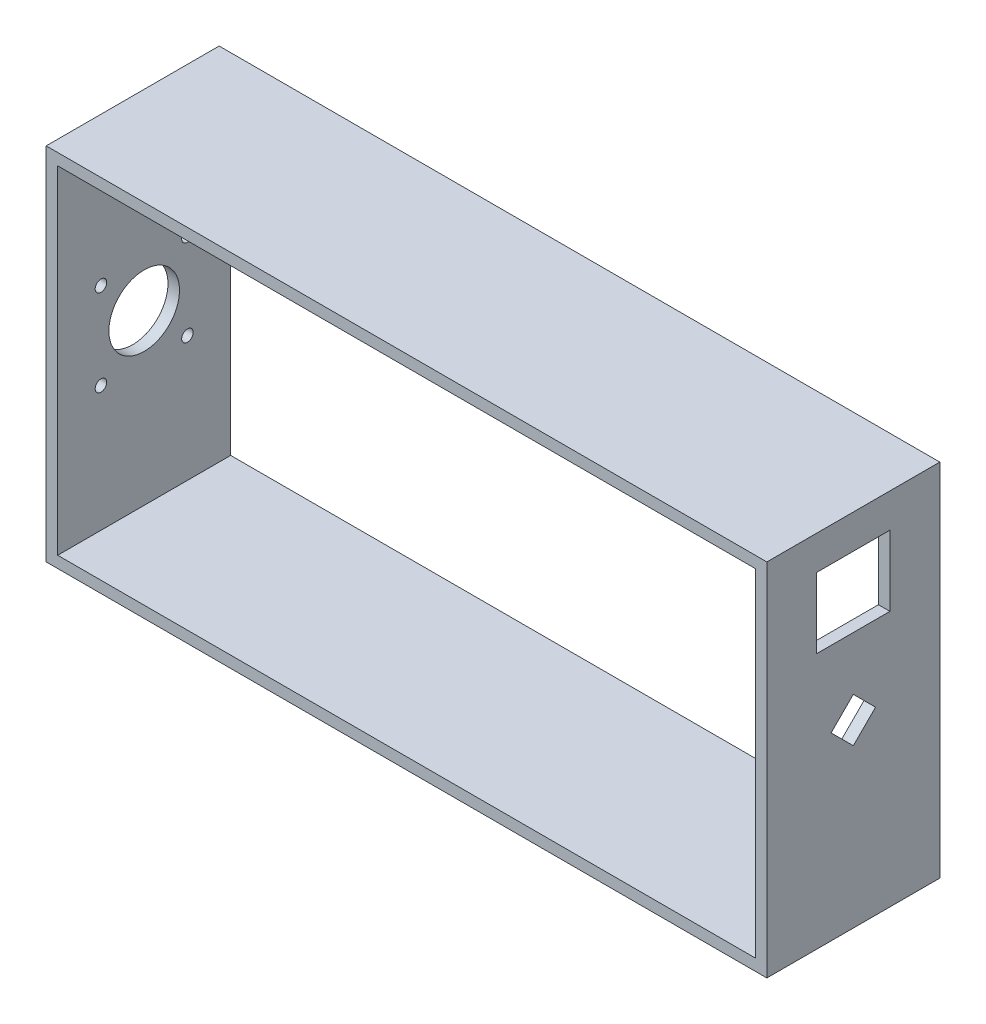
SolidWorks part; units mm, degrees
ref_plane "Ebene vorne" through (0, 0, 0) normal (0, 0, 1) x (1, 0, 0)
ref_plane "Ebene oben" through (0, 0, 0) normal (0, 1, 0) x (1, 0, 0)
ref_plane "Ebene rechts" through (0, 0, 0) normal (1, 0, 0) x (0, 0, -1)
sketch "Skizze1" plane through (0, 0, 0) normal (0, 0, 1) x (1, 0, 0)
  line L1 (0, 125) -> (250, 125)
  line L2 (0, 125) -> (0, 0)
  line L3 (0, 0) -> (250, 0)
  line L4 (250, 125) -> (250, 0)
  line L5 (246, 121) -> (4, 121)
  line L6 (246, 121) -> (246, 4)
  line L7 (246, 4) -> (4, 4)
  line L8 (4, 121) -> (4, 4)
  dimension "D1" = 250
  dimension "D2" = 125
  dimension "D3" = 4
  dimension "D4" = 4
  dimension "D5" = 4
  dimension "D6" = 4
extrude "Aufsatz-Linear austragen1" add sketch "Skizze1" along normal blind 60
sketch "Skizze2" plane through (0, 0, 0) normal (-1, 0, 0) x (0, 0, 1)
  line L0 (0, 62.5) -> (60, 62.5) construction
  line L1 (30, 125) -> (30, 0) construction
  line L2 (60, 125) -> (0, 125) construction
  line L3 (60, 0) -> (0, 0) construction
  line L4 (0, 125) -> (0, 0) construction
  line L5 (60, 125) -> (60, 0) construction
  line L6 (15, 77.5) -> (45, 77.5) construction
  line L7 (45, 77.5) -> (45, 47.5) construction
  line L8 (45, 47.5) -> (15, 47.5) construction
  line L9 (15, 47.5) -> (15, 77.5) construction
  circle A0 centre (30, 62.5) radius 12.25
  circle A1 centre (15, 77.5) radius 2
  circle A2 centre (45, 77.5) radius 2
  circle A3 centre (45, 47.5) radius 2
  circle A4 centre (15, 47.5) radius 2
  point P17 (30, 62.5)
  point P21 (30, 77.5)
  point P22 (53.5816, 62.5)
  point P24 (15, 62.5)
  dimension "D1" = 30
  dimension "D2" = 30
extrude "Schnitt-Linear austragen1" cut sketch "Skizze2" against normal blind 10
sketch "Skizze8" plane through (250, 0, 0) normal (1, 0, 0) x (0, 0, -1)
  line L0 (-60, 62.5) -> (0, 62.5) construction
  line L1 (-60, 0) -> (-60, 125) construction
  line L2 (0, 0) -> (0, 125) construction
  line L3 (-30, 125) -> (-30, 0) construction
  line L4 (-60, 125) -> (0, 125) construction
  line L5 (-60, 0) -> (0, 0) construction
  line L6 (-30, 70.2075) -> (-37.7075, 62.5)
  line L11 (-30, 70.2075) -> (-22.2925, 62.5)
  line L12 (-37.7075, 62.5) -> (-30, 54.7925)
  line L13 (-22.2925, 62.5) -> (-30, 54.7925)
  line L14 (-30, 70.2075) -> (-30, 54.7925) construction
  line L15 (-37.7075, 62.5) -> (-22.2925, 62.5) construction
  line L21 (-42.7, 113.2) -> (-17.3, 113.2)
  line L22 (-42.7, 113.2) -> (-42.7, 88.8)
  line L23 (-42.7, 88.8) -> (-17.3, 88.8)
  line L24 (-17.3, 113.2) -> (-17.3, 88.8)
  line L25 (-42.7, 113.2) -> (-17.3, 88.8) construction
  line L26 (-42.7, 88.8) -> (-17.3, 113.2) construction
  point P12 (-30, 101)
  point P13 (-30, 62.5)
  point P22 (0, 0)
  dimension "D3" = 25.4
  dimension "D4" = 24.4
  dimension "D1" = 10.9
  dimension "D2" = 10.9
  dimension "D5" = 24
extrude "Schnitt-Linear austragen6" cut sketch "Skizze8" against normal blind 22
sketch "Skizze9" plane through (250, 0, 0) normal (1, 0, 0) x (0, 0, -1)
